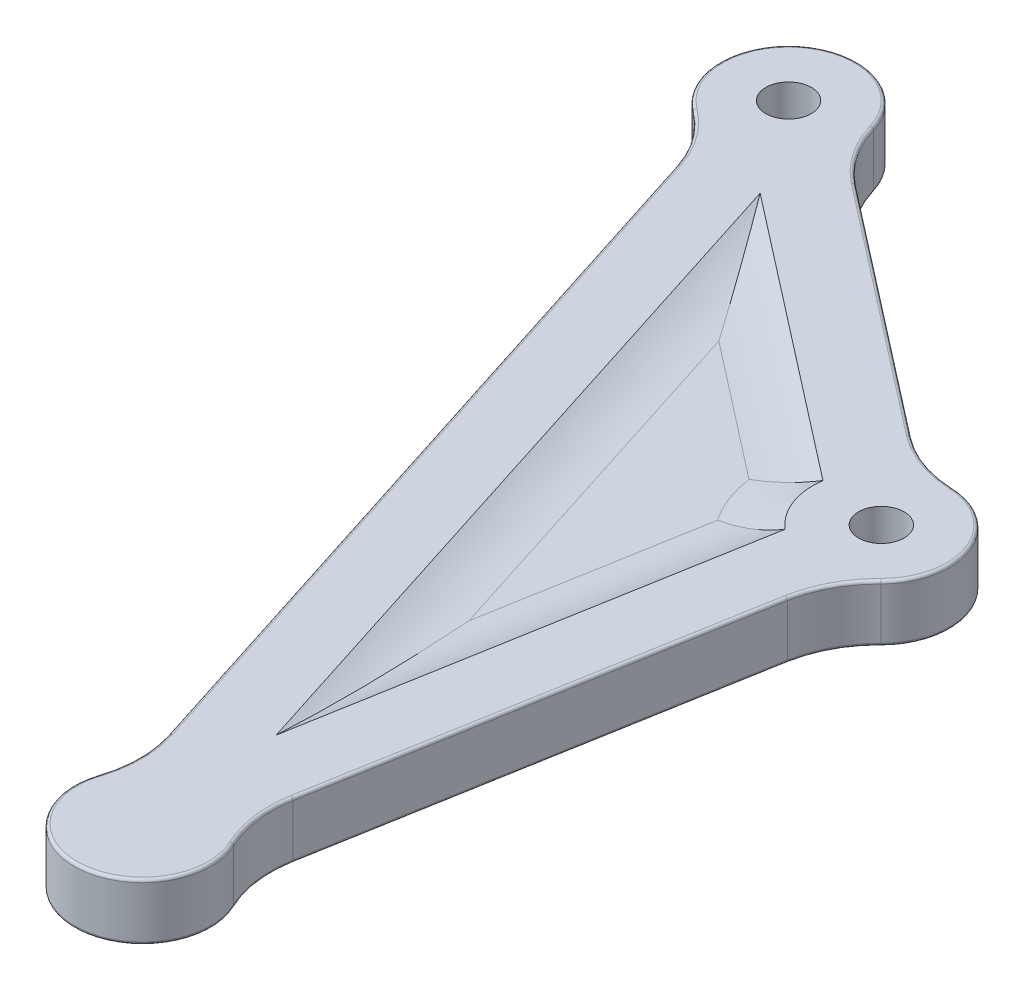
SolidWorks part; units mm, degrees
ref_plane "Front Plane" through (0, 0, 0) normal (0, 0, 1) x (1, 0, 0)
ref_plane "Top Plane" through (0, 0, 0) normal (0, 1, 0) x (1, 0, 0)
ref_plane "Right Plane" through (0, 0, 0) normal (1, 0, 0) x (0, 0, -1)
sketch "Sketch3" plane through (0, 0, 0) normal (0, 1, 0) x (1, 0, 0)
  line L0 (-52.7312, -9.4809) -> (-16.3864, -37.6776)
  line L1 (-52.7312, -9.4809) -> (-56.409, -14.2215)
  line L2 (-16.3864, -37.6776) -> (-20.0642, -42.4183)
  line L3 (-56.409, -14.2215) -> (-20.0642, -42.4183)
  line L4 (-21.2253, -39.5197) -> (-30.9369, -94.6711)
  line L5 (-21.2253, -39.5197) -> (-15.2253, -40.5762)
  line L6 (-30.9369, -94.6711) -> (-24.9369, -95.7277)
  line L7 (-15.2253, -40.5762) -> (-24.9369, -95.7277)
  line L8 (-57.4277, -12.7643) -> (-51.7124, -10.9381)
  line L9 (-57.4277, -12.7643) -> (-30.7946, -96.1126)
  line L10 (-51.7124, -10.9381) -> (-25.0793, -94.2863)
  line L11 (-30.7946, -96.1126) -> (-25.0793, -94.2863)
  circle A0 centre (-54.5701, -11.8512) radius 6
  circle A1 centre (-54.5701, -11.8512) radius 2
  circle A2 centre (-18.2253, -40.0479) radius 6
  circle A3 centre (-18.2253, -40.0479) radius 2
  circle A4 centre (-27.9369, -95.1994) radius 6
  circle A5 centre (-27.9369, -95.1994) radius 2
  dimension "D1" = 12
  dimension "D2" = 4
  dimension "D3" = 46
  dimension "D4" = 6
  dimension "D5" = 55.1515
  dimension "D6" = 6
  dimension "D7" = 6
  dimension "D8" = 87.5
sketch "Sketch4" plane through (0, 0, 0) normal (0, 1, 0) x (1, 0, 0)
  line L0 (-52.7312, -9.4809) -> (-16.3864, -37.6776) construction
  line L1 (-57.4277, -12.7643) -> (-30.7946, -96.1126) construction
  line L2 (-15.2253, -40.5762) -> (-24.9369, -95.7277) construction
  line L3 (-48.6257, -12.666) -> (-20.4919, -34.4925)
  line L4 (-55.8461, -17.7139) -> (-32.3762, -91.163)
  line L5 (-16.1218, -45.6671) -> (-24.0405, -90.6368)
  circle A0 centre (-18.2253, -40.0479) radius 6 construction
  circle A1 centre (-54.5701, -11.8512) radius 6 construction
  circle A2 centre (-27.9369, -95.1994) radius 6 construction
  arc A3 (-16.1218, -45.6671) -> (-20.4919, -34.4925) centre (-18.2253, -40.0479) ccw
  arc A4 (-48.6257, -12.666) -> (-55.8461, -17.7139) centre (-54.5701, -11.8512) ccw
  arc A5 (-32.3762, -91.163) -> (-24.0405, -90.6368) centre (-27.9369, -95.1994) ccw
extrude "Boss-Extrude1" add sketch "Sketch4" along normal mid plane 5
sketch "Sketch5" plane through (0, 0, 0) normal (0, 1, 0) x (1, 0, 0)
  circle A0 centre (-54.5701, -11.8512) radius 2 construction
  circle A1 centre (-18.2253, -40.0479) radius 2 construction
  circle A3 centre (-54.5701, -11.8512) radius 2
  circle A4 centre (-18.2253, -40.0479) radius 2
extrude "Cut-Extrude3" cut sketch "Sketch5" along normal through all both and the other way through all
sketch "Sketch6" plane through (0, 2.5, 0) normal (0, 1, 0) x (1, 0, 0)
  line L0 (-16.3864, -37.6776) -> (-20.0642, -42.4183) construction
  circle A0 centre (-18.2253, -40.0479) radius 6
  dimension "D1" = 12
sketch "Sketch7" plane through (0, -2.5, 0) normal (0, -1, 0) x (1, 0, 0)
  circle A0 centre (-18.2253, 40.0479) radius 6 construction
  circle A1 centre (-18.2253, 40.0479) radius 6
fillet "Fillet1" radius 10 6 edges at (-32.3762, 0, 91.163) (-24.0405, 0, 90.6368) (-16.1218, 0, 45.6671) (-20.4919, 0, 34.4925) (-48.6257, 0, 12.666) (-55.8461, 0, 17.7139)
fillet "Fillet2" radius 0.25 24 edges at (-23.3919, -2.5, 89.6795) (-27.5472, -2.5, 101.1867) (-33.1592, -2.5, 90.2905) (-44.1112, -2.5, 54.4384) (-55.9781, -2.5, 18.8788) (-58.0079, -2.5, 6.9338) (-47.4864, -2.5, 12.942) (-34.5588, -2.5, 23.5793) (-21.0424, -2.5, 33.4576) (-12.6331, -2.5, 37.8737) (-15.8392, -2.5, 46.7884) (-23.3919, 2.5, 89.6795) (-27.5472, 2.5, 101.1867) (-33.1592, 2.5, 90.2905) (-44.1112, 2.5, 54.4384) (-55.9781, 2.5, 18.8788) (-58.0079, 2.5, 6.9338) (-47.4864, 2.5, 12.942) (-34.5588, 2.5, 23.5793) (-21.0424, 2.5, 33.4576) (-12.6331, 2.5, 37.8737) (-15.8392, 2.5, 46.7884) (-20.0811, -2.5, 68.152) (-20.0811, 2.5, 68.152)
sketch "Sketch8" plane through (0, 2.5, 0) normal (0, 1, 0) x (1, 0, 0)
  line L0 (-56.409, -14.2215) -> (-20.0642, -42.4183) construction
  line L1 (-51.7124, -10.9381) -> (-25.0793, -94.2863) construction
  line L2 (-21.2253, -39.5197) -> (-30.9369, -94.6711) construction
  line L3 (-48.7693, -20.1485) -> (-24.1697, -39.2332)
  line L4 (-48.7693, -20.1485) -> (-28.8121, -82.6044)
  line L5 (-22.1218, -44.6106) -> (-28.8121, -82.6044)
  circle A0 centre (-18.2253, -40.0479) radius 6 construction
  arc A1 (-24.1697, -39.2332) -> (-22.1218, -44.6106) centre (-18.2253, -40.0479) ccw
extrude "Cut-Extrude4" cut sketch "Sketch8" against normal blind 1 draft 45
mirror "Mirror1" about plane through (0, 0, 0) normal (0, 1, 0) of "Cut-Extrude4"
fillet "Fillet3" radius 10 8 edges at (-24.7659, -1.5, 42.5421) (-36.0259, -1.5, 31.3007) (-37.9648, -1.5, 50.6759) (-26.1473, -1.5, 61.7047) (-37.9648, 1.5, 50.6759) (-36.0259, 1.5, 31.3007) (-24.7659, 1.5, 42.5421) (-26.1473, 1.5, 61.7047)
